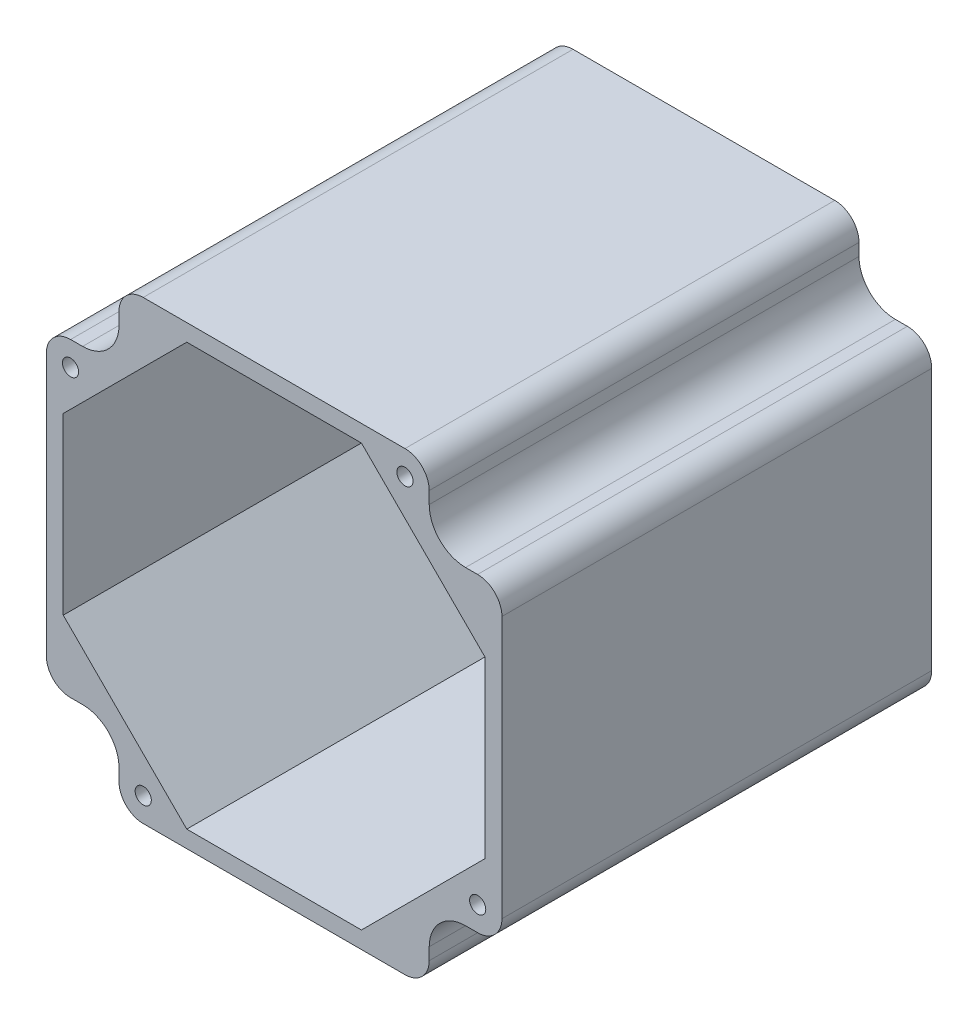
SolidWorks part; units mm, degrees
material "1060 Alloy"
ref_plane "Front Plane" through (0, 0, 0) normal (0, 0, 1) x (1, 0, 0)
ref_plane "Top Plane" through (0, 0, 0) normal (0, 1, 0) x (1, 0, 0)
ref_plane "Right Plane" through (0, 0, 0) normal (1, 0, 0) x (0, 0, -1)
sketch "Sketch1" plane through (0, 0, 0) normal (0, 0, 1) x (1, 0, 0)
  line L0 (0, 28.2) -> (0, -28.2) construction
  line L1 (-28.2, 28.2) -> (28.2, 28.2) construction
  line L2 (-28.2, 28.2) -> (-28.2, -28.2) construction
  line L3 (-28.2, -28.2) -> (28.2, -28.2) construction
  line L4 (28.2, 28.2) -> (28.2, -28.2) construction
  line L5 (-28.2, 28.2) -> (28.2, -28.2) construction
  line L6 (-28.2, -28.2) -> (28.2, 28.2) construction
  line L7 (-23.7, 23.7) -> (23.7, 23.7) construction
  line L8 (-23.7, 23.7) -> (-23.7, -23.7) construction
  line L9 (-23.7, -23.7) -> (23.7, -23.7) construction
  line L10 (23.7, 23.7) -> (23.7, -23.7) construction
  line L11 (-23.7, 23.7) -> (23.7, -23.7) construction
  line L12 (-23.7, -23.7) -> (23.7, 23.7) construction
  line L13 (-28.2, 0) -> (28.2, 0) construction
  line L14 (-23.7, 19.2) -> (-25.1852, 19.2)
  line L15 (-19.2, 23.7) -> (-19.2, 25.2)
  line L16 (16.2, -28.2) -> (-16.2, -28.2)
  line L17 (-28.2, -16.2) -> (-28.2, 16.2)
  line L18 (19.2, 23.7) -> (19.2, 25.2)
  line L19 (23.7, 19.2) -> (25.1852, 19.2)
  line L20 (28.2, 16.2) -> (28.2, -16.2)
  line L21 (16.2, 28.2) -> (-16.2, 28.2)
  line L23 (-23.7, -19.2) -> (-25.1852, -19.2)
  line L24 (-19.2, -23.7) -> (-19.2, -25.2)
  line L25 (10.811, -26.1) -> (26.1, -10.811)
  line L26 (26.1, -10.811) -> (26.1, 10.811)
  line L27 (23.7, -19.2) -> (25.1852, -19.2)
  line L28 (19.2, -23.7) -> (19.2, -25.2)
  line L29 (26.1, 10.811) -> (10.811, 26.1)
  line L30 (10.811, 26.1) -> (-10.811, 26.1)
  line L31 (-10.811, 26.1) -> (-26.1, 10.811)
  line L32 (-26.1, 10.811) -> (-26.1, -10.811)
  line L33 (-26.1, -10.811) -> (-10.811, -26.1)
  line L34 (-10.811, -26.1) -> (10.811, -26.1)
  circle A0 centre (0, 0) radius 26.1 construction
  arc A1 (-16.2, 28.2) -> (-19.2, 25.2) centre (-16.2, 25.2) ccw
  arc A2 (-28.2, 16.2) -> (-25.1852, 19.2) centre (-25.2, 16.2) cw
  arc A3 (-23.7, 19.2) -> (-19.2, 23.7) centre (-23.7, 23.7) ccw
  arc A4 (23.7, 19.2) -> (19.2, 23.7) centre (23.7, 23.7) cw
  arc A5 (28.2, 16.2) -> (25.1852, 19.2) centre (25.2, 16.2) ccw
  arc A7 (16.2, 28.2) -> (19.2, 25.2) centre (16.2, 25.2) cw
  arc A9 (-28.2, -16.2) -> (-25.1852, -19.2) centre (-25.2, -16.2) ccw
  arc A10 (-23.7, -19.2) -> (-19.2, -23.7) centre (-23.7, -23.7) cw
  arc A11 (-16.2, -28.2) -> (-19.2, -25.2) centre (-16.2, -25.2) cw
  arc A13 (28.2, -16.2) -> (25.1852, -19.2) centre (25.2, -16.2) cw
  arc A14 (23.7, -19.2) -> (19.2, -23.7) centre (23.7, -23.7) ccw
  arc A15 (16.2, -28.2) -> (19.2, -25.2) centre (16.2, -25.2) ccw
  circle A16 centre (-25.2, 16.2) radius 1
  circle A17 centre (16.2, 25.2) radius 1
  circle A18 centre (25.2, -16.2) radius 1
  circle A19 centre (-16.2, -25.2) radius 1
  point P0 (0, 0)
  point P6 (0, 0)
  dimension "D3" = 52.2
  dimension "D1" = 56.4
  dimension "D2" = 47.4
extrude "Boss-Extrude1" add sketch "Sketch1" along normal blind 53.2
sketch "Sketch2" plane through (0, 0, 0) normal (0, 0, 1) x (1, 0, 0)
  line L0 (0, 28.2) -> (0, -28.2) construction
  line L1 (-28.2, 28.2) -> (28.2, 28.2) construction
  line L2 (-28.2, 28.2) -> (-28.2, -28.2) construction
  line L3 (-28.2, -28.2) -> (28.2, -28.2) construction
  line L4 (28.2, 28.2) -> (28.2, -28.2) construction
  line L5 (-28.2, 28.2) -> (28.2, -28.2) construction
  line L6 (-28.2, -28.2) -> (28.2, 28.2) construction
  line L7 (-23.7, 23.7) -> (23.7, 23.7) construction
  line L8 (-23.7, 23.7) -> (-23.7, -23.7) construction
  line L9 (-23.7, -23.7) -> (23.7, -23.7) construction
  line L10 (23.7, 23.7) -> (23.7, -23.7) construction
  line L11 (-23.7, 23.7) -> (23.7, -23.7) construction
  line L12 (-23.7, -23.7) -> (23.7, 23.7) construction
  line L13 (-28.2, 0) -> (28.2, 0) construction
  line L14 (-23.7, 19.2) -> (-25.1852, 19.2)
  line L15 (-19.2, 23.7) -> (-19.2, 25.2)
  line L16 (16.2, -28.2) -> (-16.2, -28.2)
  line L17 (-28.2, -16.2) -> (-28.2, 16.2)
  line L18 (19.2, 23.7) -> (19.2, 25.2)
  line L19 (23.7, 19.2) -> (25.1852, 19.2)
  line L20 (28.2, 16.2) -> (28.2, -16.2)
  line L21 (16.2, 28.2) -> (-16.2, 28.2)
  line L23 (-23.7, -19.2) -> (-25.1852, -19.2)
  line L24 (-19.2, -23.7) -> (-19.2, -25.2)
  line L27 (23.7, -19.2) -> (25.1852, -19.2)
  line L28 (19.2, -23.7) -> (19.2, -25.2)
  arc A1 (-16.2, 28.2) -> (-19.2, 25.2) centre (-16.2, 25.2) ccw
  arc A2 (-28.2, 16.2) -> (-25.1852, 19.2) centre (-25.2, 16.2) cw
  arc A3 (-23.7, 19.2) -> (-19.2, 23.7) centre (-23.7, 23.7) ccw
  arc A4 (23.7, 19.2) -> (19.2, 23.7) centre (23.7, 23.7) cw
  arc A5 (28.2, 16.2) -> (25.1852, 19.2) centre (25.2, 16.2) ccw
  arc A7 (16.2, 28.2) -> (19.2, 25.2) centre (16.2, 25.2) cw
  arc A9 (-28.2, -16.2) -> (-25.1852, -19.2) centre (-25.2, -16.2) ccw
  arc A10 (-23.7, -19.2) -> (-19.2, -23.7) centre (-23.7, -23.7) cw
  arc A11 (-16.2, -28.2) -> (-19.2, -25.2) centre (-16.2, -25.2) cw
  arc A13 (28.2, -16.2) -> (25.1852, -19.2) centre (25.2, -16.2) cw
  arc A14 (23.7, -19.2) -> (19.2, -23.7) centre (23.7, -23.7) ccw
  arc A15 (16.2, -28.2) -> (19.2, -25.2) centre (16.2, -25.2) ccw
  circle A16 centre (-25.2, 16.2) radius 1
  circle A17 centre (16.2, 25.2) radius 1
  circle A18 centre (25.2, -16.2) radius 1
  circle A19 centre (-16.2, -25.2) radius 1
  point P0 (0, 0)
  point P6 (0, 0)
  dimension "D1" = 56.4
  dimension "D2" = 47.4
sketch "Sketch3" plane through (0, 0, 0) normal (1, 0, 0) x (0, 0, -1)
  line L0 (-0.15, 28.37) -> (-0.15, 28.07) construction
  line L1 (0, 28.37) -> (-0.3, 28.37) construction
  line L2 (0, 28.37) -> (0, 28.07) construction
  line L3 (0, 28.07) -> (-0.3, 28.07) construction
  line L4 (-0.3, 28.37) -> (-0.3, 28.07) construction
  line L5 (-0.3, 28.22) -> (0, 28.22) construction
  line L6 (-0.3, 28.2) -> (0, 28.2) construction
  line L7 (-0.3, 28.22) -> (0, 28.22)
  circle A0 centre (0, 28.145) radius 0.075 construction
  circle A1 centre (-0.3, 28.145) radius 0.075 construction
  circle A2 centre (-0.15, 28.145) radius 0.075 construction
  arc A3 (-0.225, 28.145) -> (-0.3, 28.22) centre (-0.3, 28.145) ccw
  arc A4 (-0.225, 28.145) -> (-0.075, 28.145) centre (-0.15, 28.145) ccw
  arc A5 (0, 28.22) -> (-0.075, 28.145) centre (0, 28.145) ccw
  dimension "D3" = 0.13
  dimension "D1" = 0.3
  dimension "D2" = 0.3
sketch "Sketch4" plane through (0, 0, 0) normal (1, 0, 0) x (0, 0, -1)
  line L0 (-53.2, 0) -> (0, 0) construction
  line L1 (-53.2, -16.2) -> (-53.2, 16.2) construction
ref_axis "Axis1" through (0, 0, 53.2) along (0, 0, -1)
sweep "Cut-Sweep4" [suppressed] cut profiles "Sketch3" path "Sketch2"
pattern_linear "LPattern3" [suppressed] count 107 spacing 0.5 along (0, 0, 1) of bodies 107
